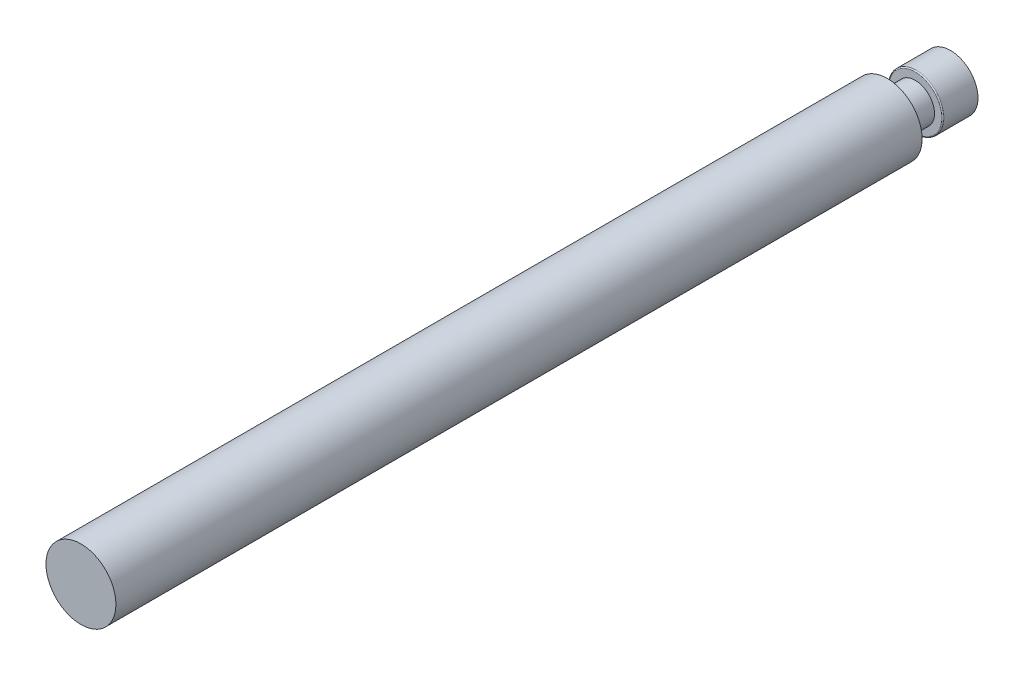
SolidWorks part; units mm, degrees
ref_plane "Plano frontal" through (0, 0, 0) normal (0, 0, 1) x (1, 0, 0)
ref_plane "Plano superior" through (0, 0, 0) normal (0, 1, 0) x (1, 0, 0)
ref_plane "Plano direito" through (0, 0, 0) normal (1, 0, 0) x (0, 0, -1)
sketch "Esboço1" plane through (0, 0, 0) normal (0, 0, 1) x (1, 0, 0)
  circle A0 centre (0, 0) radius 6.35
  dimension "D1" = 12.7
extrude "Ressalto-extrusão1" add sketch "Esboço1" along normal blind 160
sketch "Esboço2" plane through (0, 0, 0) normal (0, 0, -1) x (-1, 0, 0)
  circle A0 centre (0, 0) radius 5
  dimension "D1" = 10
extrude "Corte-extrusão1" cut sketch "Esboço2" against normal blind 12 flip side to cut
cosmetic thread "Representação de rosca1" parameters "D1"=8.4, "D2"=6.891
sketch "Esboço4" plane through (0, 0, 12) normal (0, 0, -1) x (-1, 0, 0)
  circle A0 centre (0, 0) radius 3.5
  dimension "D1" = 7
extrude "Corte-extrusão2" cut sketch "Esboço4" along normal blind 3.6 flip side to cut
fillet "Filete1" radius 0.2 1 edges at (-5, 0, 8.4)
ref_axis "Eixo1" through (0, 0, 160) along (0, 0, -1)
chamfer "Chanfro2" distance 2 angle 60 1 edges at (-5, 0, 0) first distance on face at (-5, 0, 8.2)
chamfer "Chanfro3" distance 1.5 angle 60 1 edges at (-6.35, 0, 12) first distance on face at (6.35, 0, 160)
